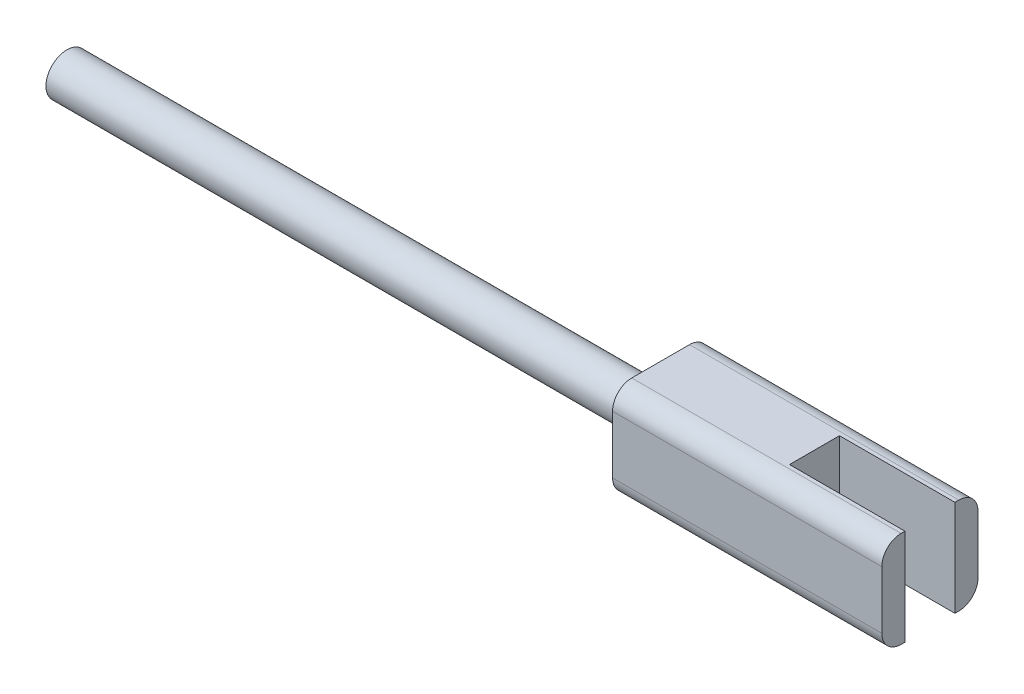
SolidWorks part; units mm, degrees
ref_plane "Front Plane" through (0, 0, 0) normal (0, 0, 1) x (1, 0, 0)
ref_plane "Top Plane" through (0, 0, 0) normal (0, 1, 0) x (1, 0, 0)
ref_plane "Right Plane" through (0, 0, 0) normal (1, 0, 0) x (0, 0, -1)
sketch "Sketch1" plane through (0, 0, 0) normal (1, 0, 0) x (0, 0, -1)
  circle A0 centre (0, 0) radius 1.09
extrude "Boss-Extrude1" add sketch "Sketch1" along normal blind 32.87
ref_plane "Plane1" through (30.87, 0, 0) normal (1, 0, 0) x (0, 0, -1)
sketch "Sketch2" plane through (30.87, 0, 0) normal (1, 0, 0) x (0, 0, -1)
  line L0 (-1.5, -2.5) -> (1.5, -2.5)
  line L1 (2.5, -1.5) -> (2.5, 1.5)
  line L2 (1.5, 2.5) -> (-1.5, 2.5)
  line L3 (-2.5, 1.5) -> (-2.5, -1.5)
  arc A0 (1.5, -2.5) -> (2.5, -1.5) centre (1.5, -1.5) ccw
  arc A1 (2.5, 1.5) -> (1.5, 2.5) centre (1.5, 1.5) ccw
  arc A2 (-1.5, 2.5) -> (-2.5, 1.5) centre (-1.5, 1.5) ccw
  arc A3 (-2.5, -1.5) -> (-1.5, -2.5) centre (-1.5, -1.5) ccw
extrude "Boss-Extrude2" add sketch "Sketch2" along normal blind 14
sketch "Sketch3" plane through (0, 0, 0) normal (0, 1, 0) x (1, 0, 0)
  line L0 (38.87, 1.3) -> (45.87, 1.3)
  line L1 (45.87, 1.3) -> (45.87, -1.3)
  line L2 (45.87, -1.3) -> (38.87, -1.3)
  line L3 (38.87, -1.3) -> (38.87, 1.3)
extrude "Cut-Extrude1" cut sketch "Sketch3" against normal through all and the other way through all
